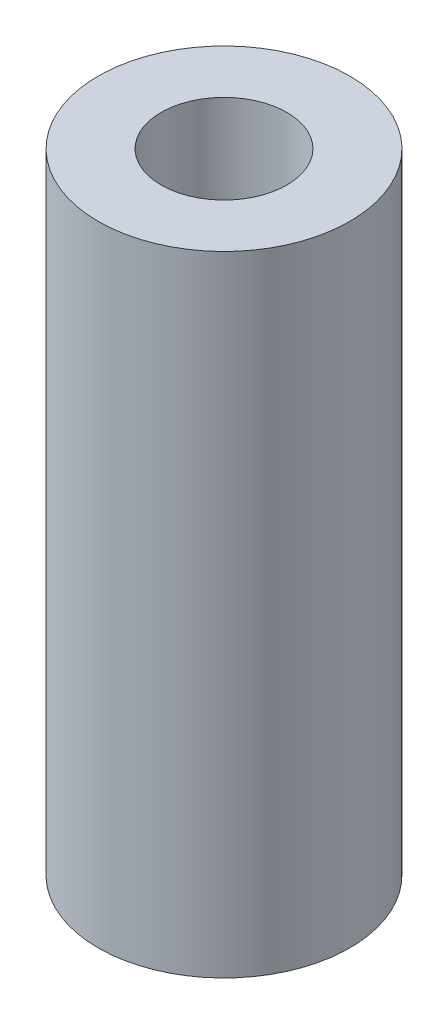
SolidWorks part; units mm, degrees
ref_plane "Front Plane" through (0, 0, 0) normal (0, 0, 1) x (1, 0, 0)
ref_plane "Top Plane" through (0, 0, 0) normal (0, 1, 0) x (1, 0, 0)
ref_plane "Right Plane" through (0, 0, 0) normal (1, 0, 0) x (0, 0, -1)
sketch "Sketch1" plane through (0, 0, 0) normal (0, 1, 0) x (1, 0, 0)
  circle A0 centre (0, 0) radius 50.8
  circle A1 centre (0, 0) radius 25.4
  dimension "D1" = 101.6
  dimension "D2" = 50.8
extrude "Boss-Extrude1" add sketch "Sketch1" along normal blind 254
equation "\"Body_Tube_OD\"= 4in"
equation "\"Body_Tube_ID\"= 2in"
equation "\"D1@Sketch1\"=\"Body_Tube_OD\""
equation "\"D2@Sketch1\"=\"Body_Tube_ID\""
equation "\"Mid_Section_Length\" = 10in"
equation "\"D1@Boss-Extrude1\"=\"Mid_Section_Length\""
